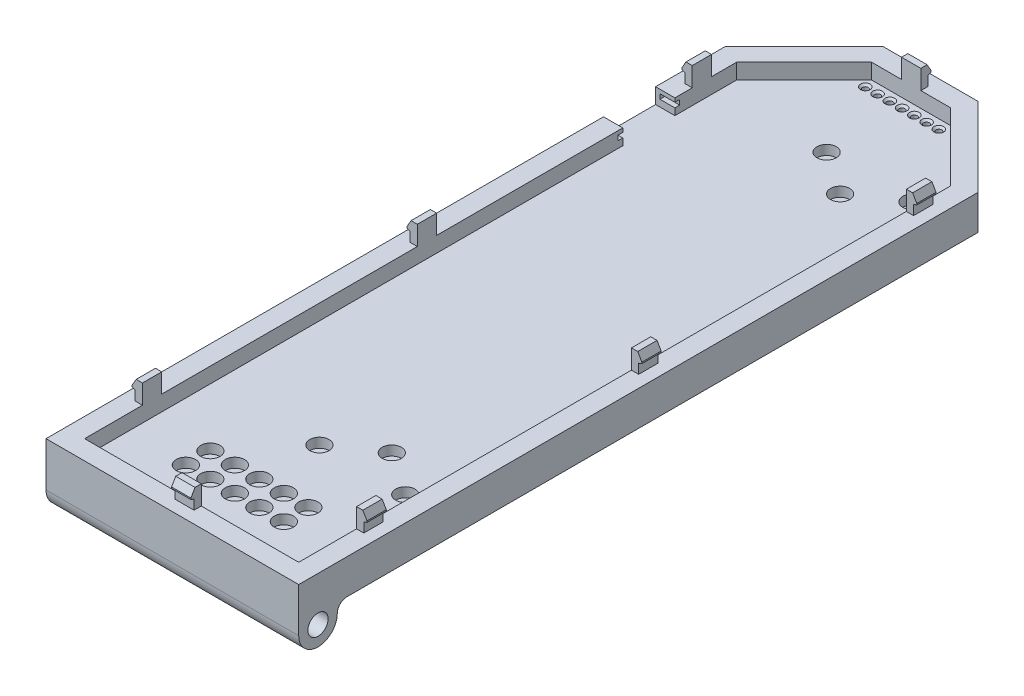
SolidWorks part; units mm, degrees
ref_plane "Front Plane" through (0, 0, 0) normal (0, 0, 1) x (1, 0, 0)
ref_plane "Top Plane" through (0, 0, 0) normal (0, 1, 0) x (1, 0, 0)
ref_plane "Right Plane" through (0, 0, 0) normal (1, 0, 0) x (0, 0, -1)
sketch "Sketch1" plane through (0, 0, 0) normal (0, 1, 0) x (1, 0, 0)
  line L0 (0, 0) -> (-11.1, 0)
  line L5 (-11.1, 0) -> (-11.1, 67.6)
  line L6 (-11.1, 67.6) -> (-4.1, 74.6)
  line L7 (-4.1, 74.6) -> (0, 74.6)
  line L8 (0, 74.6) -> (0, 0) construction
  line L9 (0, 0) -> (11.1, 0)
  line L10 (4.1, 74.6) -> (0, 74.6)
  line L11 (11.1, 67.6) -> (4.1, 74.6)
  line L12 (11.1, 0) -> (11.1, 67.6)
  dimension "D1" = 4.1
  dimension "D2" = 135
  dimension "D3" = 74.6
  dimension "D4" = 11.1
sketch "Sketch2" plane through (0, 0, 0) normal (0, 1, 0) x (1, 0, 0)
  line L4 (0, -2) -> (-13.1, -2)
  line L9 (-13.1, -2) -> (-13.1, 68.4284)
  line L10 (-13.1, 68.4284) -> (-4.9284, 76.6)
  line L11 (-4.9284, 76.6) -> (0, 76.6)
  line L12 (-11.1, 67.6) -> (-4.1, 74.6) construction
  line L13 (-4.1, 74.6) -> (0, 74.6) construction
  line L14 (-11.1, 0) -> (-11.1, 67.6) construction
  line L15 (0, 0) -> (-11.1, 0) construction
  line L16 (0, 76.6) -> (0, -2) construction
  line L17 (4.9284, 76.6) -> (0, 76.6)
  line L18 (13.1, 68.4284) -> (4.9284, 76.6)
  line L19 (13.1, -2) -> (13.1, 68.4284)
  line L20 (0, -2) -> (13.1, -2)
  dimension "D1" = 2
  dimension "D2" = 2
  dimension "D3" = 2
  dimension "D4" = 2
extrude "Boss-Extrude1" add sketch "Sketch2" along normal blind 3.6
extrude "Cut-Extrude1" cut sketch "Sketch1" against normal blind 1.6 from surface starting at face at (0, 3.6, -47.6761)
sketch "Sketch3" plane through (0, 2, 0) normal (0, 1, 0) x (1, 0, 0)
  circle A0 centre (-3.81, 73.66) radius 0.3
  dimension "D1" = 0.6
extrude "Cut-Extrude2" cut sketch "Sketch3" against normal through all
sketch "Sketch5" plane through (0, 0, 0) normal (0, -1, 0) x (-1, 0, 0)
  line L0 (3.81, 73.66) -> (0.0139, 73.66) construction
  line L1 (0.0139, 73.66) -> (-3.7823, 73.66) construction
  line L2 (3.81, 73.66) -> (-3.7823, 73.66) construction
  line L3 (3.81, 72.41) -> (-3.7823, 72.41)
  line L4 (3.81, 74.91) -> (-3.7823, 74.91)
  arc A0 (3.81, 72.41) -> (3.81, 74.91) centre (3.81, 73.66) ccw
  arc A1 (-3.7823, 74.91) -> (-3.7823, 72.41) centre (-3.7823, 73.66) ccw
  point P0 (0.0139, 73.66)
  dimension "D1" = 2.5
extrude "Boss-Extrude3" add sketch "Sketch5" along normal blind 3 draft 10
extrude "Cut-Extrude3" cut sketch "Sketch3<2>" against normal through all
sketch "Sketch3<2>" plane through (0, 2, 0) normal (0, 1, 0) x (1, 0, 0) same geometry as "Sketch3"
pattern_linear "LPattern5" count 7 spacing 1.27 along (1, 0, 0) of "Cut-Extrude3"
chamfer "Chamfer2" distance 0.2 angle 45 7 edges at (3.81, 2, -73.36) (2.54, 2, -73.36) (1.27, 2, -73.36) (0, 2, -73.36) (-1.27, 2, -73.36) (-2.54, 2, -73.36) (-3.81, 2, -73.36)
fillet "Fillet2" radius 1 4 edges at (5.0323, 0, -73.66) (-0.0139, 0, -74.91) (-5.06, 0, -73.66) (-0.0139, 0, -72.41)
sketch "Sketch6" plane through (-13.1, 0, 0) normal (-1, 0, 0) x (0, 0, 1)
  line L3 (2, -1) -> (2, 0)
  line L4 (-2, -1) -> (-2, 0)
  line L5 (-68.4284, 0) -> (2, 0) construction
  line L6 (-2, 0) -> (2, 0)
  arc A0 (2, -1) -> (-2, -1) centre (0, -1) cw
  line M2 (-68.4284, 0) -> (2, 0)
  dimension "D1" = 2
  dimension "D2" = 1
extrude "Boss-Extrude4" add sketch "Sketch6" against normal up to surface (26.2 mm away) contours A0 M2 region at (-13.1, -1.3242, 0) up to face at (13.1, 1.8, -33.2142)
sketch "Sketch7" plane through (-13.1, 0, 0) normal (-1, 0, 0) x (0, 0, 1)
  circle A0 centre (0, -1) radius 1.05
  arc A3 (-2, -1) -> (2, -1) centre (0, -1) ccw construction
  dimension "D1" = 2.1
extrude "Cut-Extrude4" cut sketch "Sketch7" against normal through all
sketch "Sketch8" plane through (0, 3.6, 0) normal (0, 1, 0) x (1, 0, 0)
  line L1 (-13.1, 55.8) -> (-9.1, 55.8)
  line L2 (-13.1, 55.8) -> (-13.1, 61.2)
  line L3 (-13.1, 61.2) -> (-9.1, 61.2)
  line L4 (-9.1, 55.8) -> (-9.1, 61.2)
  line L5 (-13.1, 55.8) -> (-9.1, 61.2) construction
  line L6 (-13.1, 61.2) -> (-9.1, 55.8) construction
  line L7 (-13.1, 68.4284) -> (-13.1, -2) construction
  point P0 (-11.1, 58.5)
  dimension "D1" = 5.4
  dimension "D2" = 4
extrude "Cut-Extrude5" cut sketch "Sketch8" against normal up to surface (1.6 mm away) up to face at (3.81, 2, -74.16)
sketch "Sketch9" plane through (0, 2, 0) normal (0, 1, 0) x (1, 0, 0)
  circle A0 centre (-5.08, 4.48) radius 1
  dimension "D1" = 2
extrude "Cut-Extrude7" cut sketch "Sketch9" against normal blind 1
pattern_linear "LPattern6" count 5 spacing 2.54 along (1, 0, 0) count 2 spacing 2.54 along (0, 0, -1) of "Cut-Extrude7"
sketch "Sketch10" plane through (0, 2, 0) normal (0, 1, 0) x (1, 0, 0)
  line L0 (11.1, 39.491) -> (-11.1, 39.491) construction
  line L1 (11.1, 0) -> (11.1, 67.6) construction
  line L2 (-11.1, 55.8) -> (-11.1, 0) construction
  circle A1 centre (0.05, 13.2) radius 1
  circle A3 centre (4.5, 16.25) radius 1
  circle A4 centre (8.95, 13.2) radius 1
  circle A5 centre (8.95, 65.782) radius 1
  circle A6 centre (4.5, 62.732) radius 1
  circle A7 centre (0.05, 65.782) radius 1
  dimension "D1" = 2
  dimension "D2" = 3.05
  dimension "D3" = 4.45
  dimension "D4" = 3.05
  dimension "D5" = 4.45
  dimension "D6" = 23.241
extrude "Cut-Extrude8" cut sketch "Sketch10" against normal blind 1
ref_plane "Plane2" through (0, 0, -7) normal (0, 0, 1) x (1, 0, 0)
sketch "Sketch11" plane through (0, 0, -7) normal (0, 0, 1) x (1, 0, 0)
  line L0 (-11.1, 3.6) -> (-11.1, 5.6)
  line L1 (-11.75, 5.6) -> (-12.18, 4.8552)
  line L2 (-12.18, 4.8552) -> (-12.18, 4.7201)
  line L3 (-12.18, 4.7201) -> (-11.85, 4.6)
  line L4 (-11.85, 4.6) -> (-11.85, 3.6)
  line L5 (-11.85, 3.6) -> (-11.1, 3.6)
  line L6 (-11.1, 5.6) -> (-11.75, 5.6)
  line L7 (-13.1, 3.6) -> (13.1, 3.6) construction
  dimension "D1" = 0.75
  dimension "D2" = 0.33
  dimension "D3" = 120
  dimension "D4" = 110
  dimension "D5" = 1
  dimension "D6" = 2
  dimension "D7" = 0.65
extrude "Boss-Extrude5" add sketch "Sketch11" along normal blind 1 and the other way blind 1
pattern_linear "LPattern7" count 3 spacing 28.5 along (0, 0, -1) of "Boss-Extrude5"
mirror "Mirror1" about plane through (0, 0, 0) normal (1, 0, 0) of "LPattern7"
sketch "Sketch13" plane through (0, 0, 0) normal (1, 0, 0) x (0, 0, -1)
  line L0 (0, 3.6) -> (0, 5.6)
  line L1 (-0.65, 5.6) -> (-1.08, 4.8552)
  line L2 (-1.08, 4.8552) -> (-1.08, 4.7201)
  line L3 (-1.08, 4.7201) -> (-0.75, 4.6)
  line L4 (-0.75, 4.6) -> (-0.75, 3.6)
  line L5 (-0.75, 3.6) -> (0, 3.6)
  line L6 (0, 5.6) -> (-0.65, 5.6)
  dimension "D1" = 0.75
  dimension "D2" = 0.33
  dimension "D3" = 120
  dimension "D4" = 110
  dimension "D5" = 1
  dimension "D6" = 2
  dimension "D7" = 0.65
extrude "Boss-Extrude6" add sketch "Sketch13" along normal blind 1 and the other way blind 1
ref_plane "Plane3" through (0, 0, -37.3) normal (0, 0, 1) x (1, 0, 0)
mirror "Mirror2" about plane through (0, 0, -37.3) normal (0, 0, 1) of "Boss-Extrude6"
sketch "Sketch14" plane through (-11.1, 0, 0) normal (1, 0, 0) x (0, 0, -1)
  line L1 (55.3, 3.2) -> (61.7, 3.2)
  line L2 (55.3, 3.2) -> (55.3, 2.7)
  line L3 (55.3, 2.7) -> (61.7, 2.7)
  line L4 (61.7, 3.2) -> (61.7, 2.7)
  line L5 (55.3, 2.95) -> (61.7, 2.95) construction
  line L6 (55.8, 2) -> (0, 2) construction
  line L7 (55.8, 2) -> (55.8, 3.6) construction
  line L8 (61.2, 3.6) -> (61.2, 2) construction
  dimension "D1" = 0.95
  dimension "D2" = 0.5
  dimension "D3" = 0.5
  dimension "D4" = 0.5
extrude "Cut-Extrude9" cut sketch "Sketch14" against normal blind 1.55 contours L1 L4 L3 L2
fillet "Fillet3" radius 1 1 edges at (0, 0, -2)
sketch "Sketch15" plane through (0, 0, 0) normal (0, -1, 0) x (1, 0, 0)
  circle A0 centre (0, -10) radius 2.794
  point P2 (0, 0)
  dimension "D2" = 5.588
  dimension "D1" = 10
extrude "Cut-Extrude10" cut sketch "Sketch15" against normal blind 0.25
